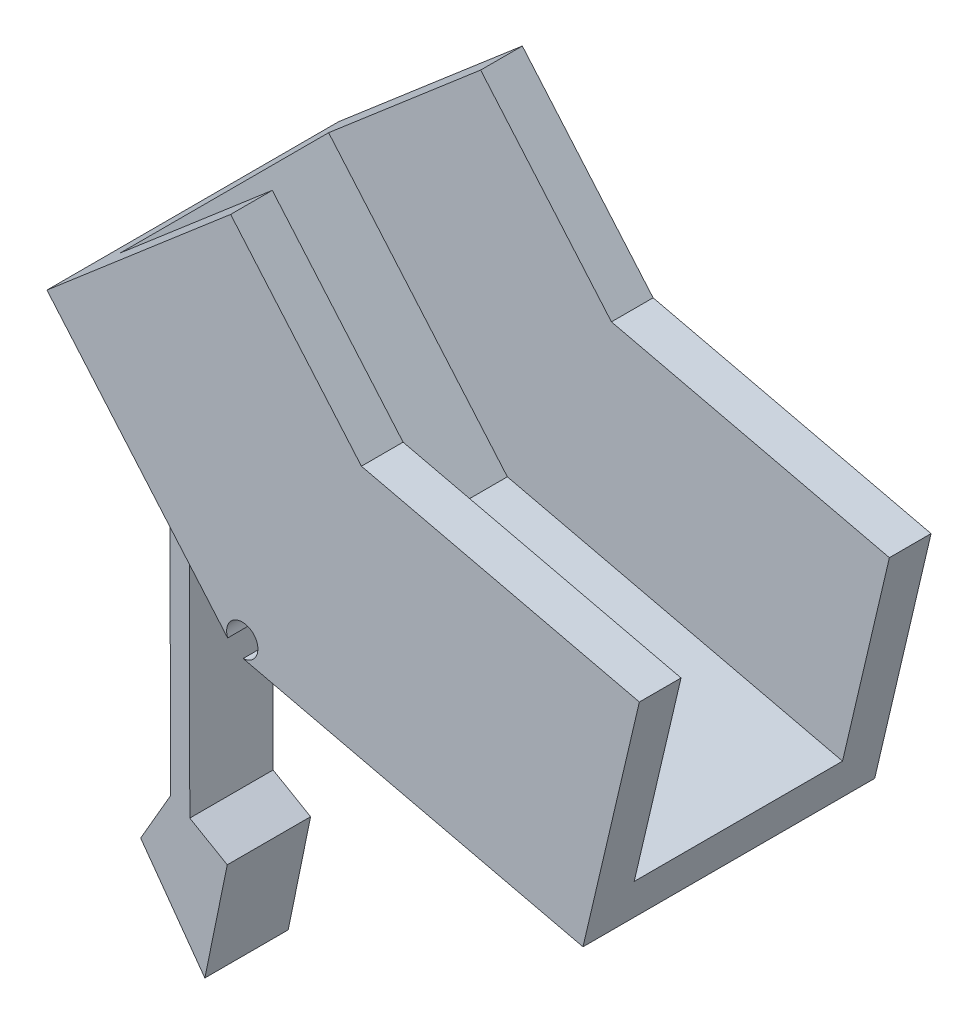
SolidWorks part; units mm, degrees
note: The reader was unsure of these and kept them because the rebuilt part matched: shared geometry of "Sketch2<2>".
ref_plane "Front Plane" through (0, 0, 0) normal (0, 0, 1) x (1, 0, 0)
ref_plane "Top Plane" through (0, 0, 0) normal (0, 1, 0) x (1, 0, 0)
ref_plane "Right Plane" through (0, 0, 0) normal (1, 0, 0) x (0, 0, -1)
sketch "Sketch1" plane through (-21.3268, -3.6119, 0) normal (0, 0, 1) x (1, 0, 0)
  line L0 (40.8373, 20.6265) -> (49.8422, 10.116)
  line L1 (49.8422, 10.116) -> (66.5653, 6.1913)
  point P2 (57.3815, 5.358)
  point P4 (41.2287, 13.5158)
  point P5 (77.9777, 3.3016)
  point P6 (41.1613, 15.35)
  point P7 (54.5766, 4.8555)
  point P8 (42.4641, 20.7047)
  point P9 (49.8422, 10.116)
  point P10 (40.8373, 20.6265)
  point P11 (0, 0)
  point P12 (0, 0)
  point P13 (66.5653, 6.1913)
extrude "Extrude-Thin1" add sketch "Sketch1" along normal blind 10 thin thin type one direction reverse wall 2
sketch "Sketch2" plane through (0, 0, 10) normal (0, 0, 1) x (1, 0, 0)
  line L0 (19.5104, 17.0146) -> (28.3261, 24.5673)
  line L1 (28.3261, 24.5673) -> (34.6041, 17.2397)
  line L2 (34.6041, 17.2397) -> (47.9443, 14.1089)
  line L3 (47.9443, 14.1089) -> (45.2385, 2.5793)
  line L4 (45.6955, 4.5264) -> (45.2385, 2.5793) construction
  line L5 (19.5104, 17.0146) -> (21.0292, 18.3158) construction
  line L7 (21.0292, 18.3158) -> (29.6088, 8.3017) construction
  line L8 (29.6088, 8.3017) -> (45.6955, 4.5264) construction
  line L15 (28.5153, 6.504) -> (45.2385, 2.5793)
  line L16 (45.2385, 2.5793) -> (45.6955, 4.5264)
  line L17 (45.6955, 4.5264) -> (29.6088, 8.3017)
  line L18 (29.6088, 8.3017) -> (21.0292, 18.3158)
  line L19 (21.0292, 18.3158) -> (19.5104, 17.0146)
  line L20 (19.5104, 17.0146) -> (28.5153, 6.504)
  line L21 (28.5153, 6.504) -> (45.2385, 2.5793)
  line L26 (19.5104, 17.0146) -> (28.5153, 6.504)
  point P15 (0, 0)
  dimension "D1" = 11.6086
  dimension "D2" = 11.8428
  dimension "D3" = 0
extrude "Boss-Extrude1" add sketch "Sketch2" along normal blind 2
extrude "Boss-Extrude2" add sketch "Sketch2<2>" against normal blind 2 from surface at -10 starting at face at (31.5996, 9.5403, 0)
sketch "Sketch2<2>" plane through (0, 0, 10) normal (0, 0, 1) x (1, 0, 0) same geometry as "Sketch2"
sketch "Sketch3" plane through (0, 0, 12) normal (0, 0, 1) x (1, 0, 0)
  line L0 (34.6041, 17.2397) -> (28.5153, 6.504) construction
  circle A0 centre (28.8853, 7.1564) radius 0.75
  point P6 (0, 0)
  dimension "D1" = 1.5
extrude "Cut-Extrude1" cut sketch "Sketch3" against normal through all
sketch "Sketch4" plane through (0, 0, 12) normal (0, 0, 1) x (1, 0, 0)
  line L3 (25.4477, 10.0846) -> (21.4233, 6.6367)
  line L4 (21.4233, 6.6367) -> (21.4347, -5.0514)
  line L5 (21.4347, -5.0514) -> (20.0087, -7.5135)
  line L6 (20.0087, -7.5135) -> (23.0899, -11.7902)
  line L7 (23.0899, -11.7902) -> (24.1645, -6.548)
  line L8 (24.1645, -6.548) -> (22.3657, -5.5062)
  line L9 (22.3657, -5.5062) -> (22.3549, 5.5494)
  line L10 (22.3549, 5.5494) -> (26.3792, 8.9973)
  line L11 (26.3792, 8.9973) -> (25.4477, 10.0846)
  line L12 (28.1839, 6.8909) -> (19.5104, 17.0146) construction
extrude "Boss-Extrude3" add sketch "Sketch4" along normal blind 4 from offset 8 offset against normal yes
